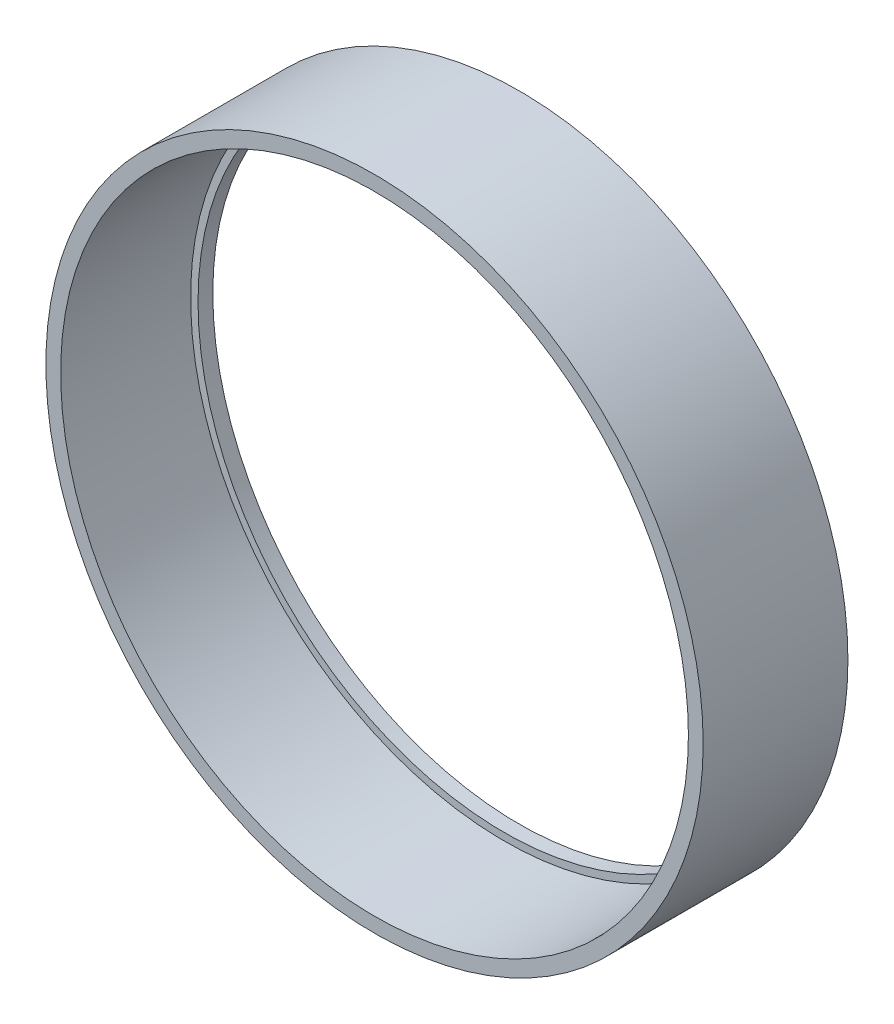
SolidWorks part; units mm, degrees
material "Plain Carbon Steel"
ref_plane "Front Plane" through (0, 0, 0) normal (0, 0, 1) x (1, 0, 0)
ref_plane "Top Plane" through (0, 0, 0) normal (0, 1, 0) x (1, 0, 0)
ref_plane "Right Plane" through (0, 0, 0) normal (1, 0, 0) x (0, 0, -1)
sketch "Sketch1" plane through (0, 0, 0) normal (0, 0, 1) x (1, 0, 0)
  circle A0 centre (0, 0) radius 21.25
  circle A1 centre (0, 0) radius 22.25
  circle A2 centre (0, 0) radius 20.75
  dimension "D1" = 44.5
  dimension "D2" = 42.5
  dimension "D3" = 41.5
extrude "Boss-Extrude1" add sketch "Sketch1" along normal blind 9.8 contours A1 A0 region at (-21.6207, 0, 0)
extrude "Boss-Extrude2" add sketch "Sketch1<3>" along normal blind 1 contours A0 A2 region at (-21.1899, 0, 0)
sketch "Sketch1<3>" plane through (0, 0, 0) normal (0, 0, 1) x (1, 0, 0) same geometry as "Sketch1"
